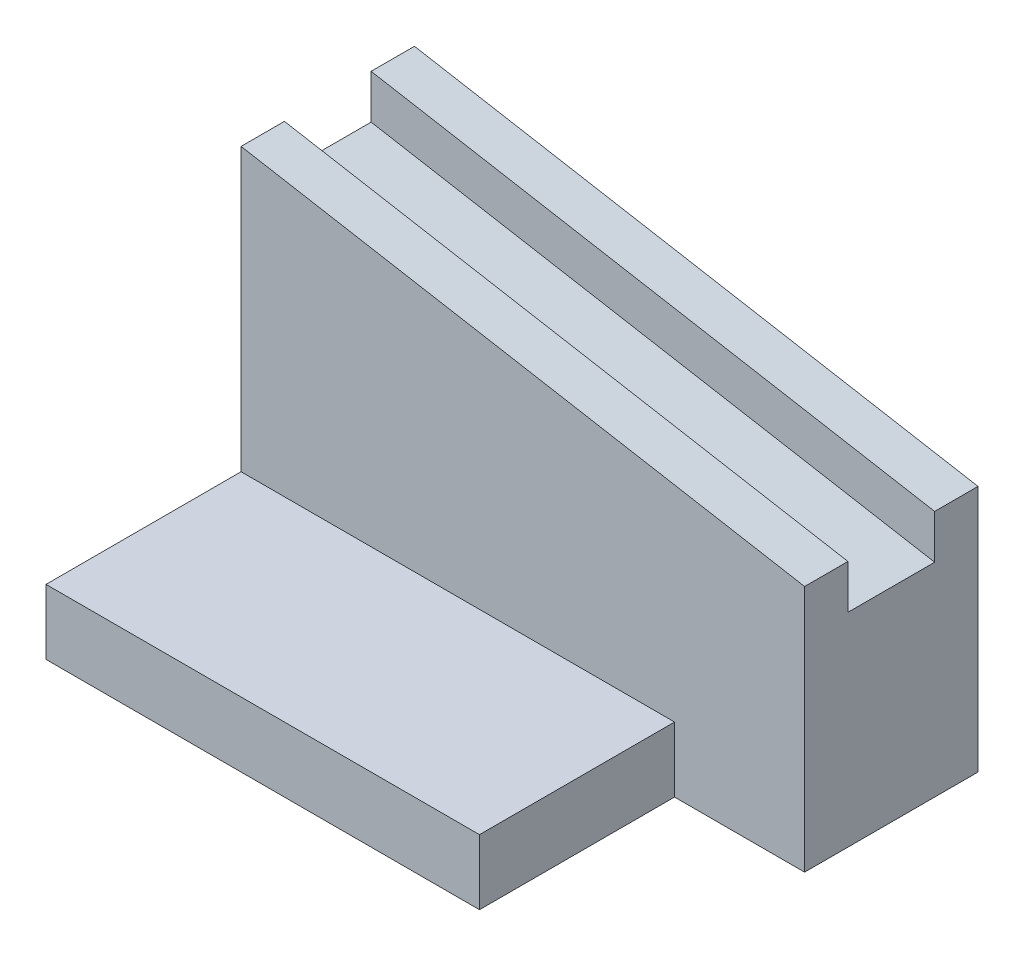
SolidWorks part; units mm, degrees
ref_plane "Plano frontal" through (0, 0, 0) normal (0, 0, 1) x (1, 0, 0)
ref_plane "Plano superior" through (0, 0, 0) normal (0, 1, 0) x (1, 0, 0)
ref_plane "Plano direito" through (0, 0, 0) normal (1, 0, 0) x (0, 0, -1)
sketch "Esboço1" plane through (0, 0, 0) normal (0, 0, 1) x (1, 0, 0)
  line L0 (-53.2953, 9.3008) -> (76.7047, 9.3008)
  line L1 (-53.2953, 9.3008) -> (-53.2953, 89.3008)
  line L2 (76.7047, 9.3008) -> (76.7047, 66.3783)
  line L3 (-53.2953, 89.3008) -> (76.7047, 66.3783)
  dimension "D1" = 100
  dimension "D2" = 80
  dimension "D3" = 130
extrude "Ressalto-extrusão1" add sketch "Esboço1" along normal blind 40
sketch "Esboço3" [suppressed] plane through (13.6643, 77.494, 0) normal (0.1736, 0.9848, 0) x (0.9848, -0.1736, 0)
  line L0 (64.0129, -40) -> (-67.9926, -40) construction
  line L1 (-71.0201, -30) -> (70.4962, -30)
  line L2 (-71.0201, -30) -> (-71.0201, -10)
  line L3 (-71.0201, -10) -> (70.4962, -10)
  line L4 (70.4962, -30) -> (70.4962, -10)
  line L5 (64.0129, 0) -> (-67.9926, 0) construction
  dimension "D1" = 10
  dimension "D2" = 10
extrude "Corte-extrusão2" [suppressed] cut sketch "Esboço3" against normal blind 10
sketch "Esboço4" plane through (13.6643, 77.494, 0) normal (0.1736, 0.9848, 0) x (0.9848, -0.1736, 0)
  line L0 (64.0129, 0) -> (-67.9926, 0) construction
  line L1 (-77.3839, -10) -> (94.2466, -10)
  line L2 (-77.3839, -10) -> (-77.3839, -30)
  line L3 (-77.3839, -30) -> (94.2466, -30)
  line L4 (94.2466, -10) -> (94.2466, -30)
  line L5 (64.0129, -40) -> (-67.9926, -40) construction
  dimension "D1" = 10
  dimension "D2" = 10
extrude "Corte-extrusão3" cut sketch "Esboço4" against normal blind 10
sketch "Esboço5" plane through (0, 0, 40) normal (0, 0, 1) x (1, 0, 0)
  line L1 (-53.2953, 9.3008) -> (46.7047, 9.3008)
  line L2 (-53.2953, 9.3008) -> (-53.2953, 24.3008)
  line L3 (-53.2953, 24.3008) -> (46.7047, 24.3008)
  line L4 (46.7047, 9.3008) -> (46.7047, 24.3008)
  dimension "D1" = 15
  dimension "D2" = 100
extrude "Ressalto-extrusão2" add sketch "Esboço5" along normal blind 45
